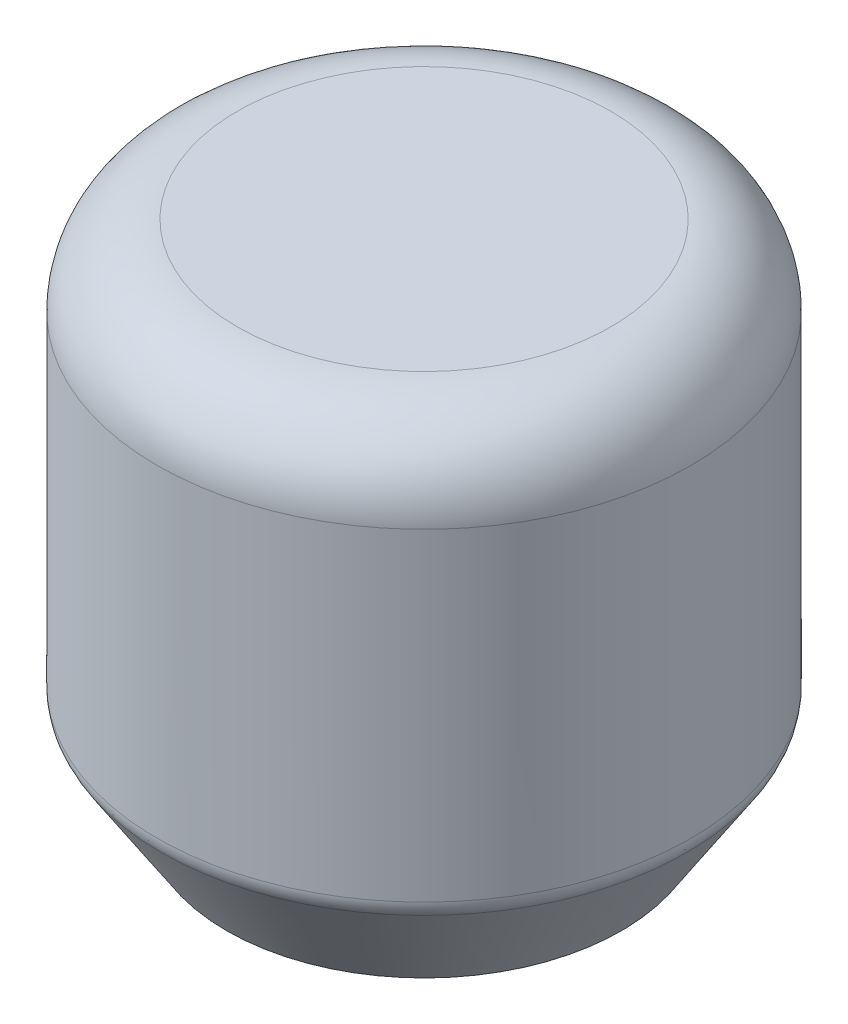
SolidWorks part; units mm, degrees
ref_plane "Front Plane" through (0, 0, 0) normal (0, 0, 1) x (1, 0, 0)
ref_plane "Top Plane" through (0, 0, 0) normal (0, 1, 0) x (1, 0, 0)
ref_plane "Right Plane" through (0, 0, 0) normal (1, 0, 0) x (0, 0, -1)
sketch "Sketch1" plane through (0, 0, 0) normal (0, 1, 0) x (1, 0, 0)
  circle A1 centre (0, 0) radius 127
extrude "Boss-Extrude1" add sketch "Sketch1" along normal blind 246.38 contours A1
fillet "Fillet1" radius 38.1 1 edges at (0, 246.38, 127)
chamfer "Chamfer1" distance 33.02 angle 57 1 edges at (0, 0, 127) first distance on face at (0, 0, 127)
fillet "Fillet2" radius 12.7 1 edges at (0, 50.8463, 127)
